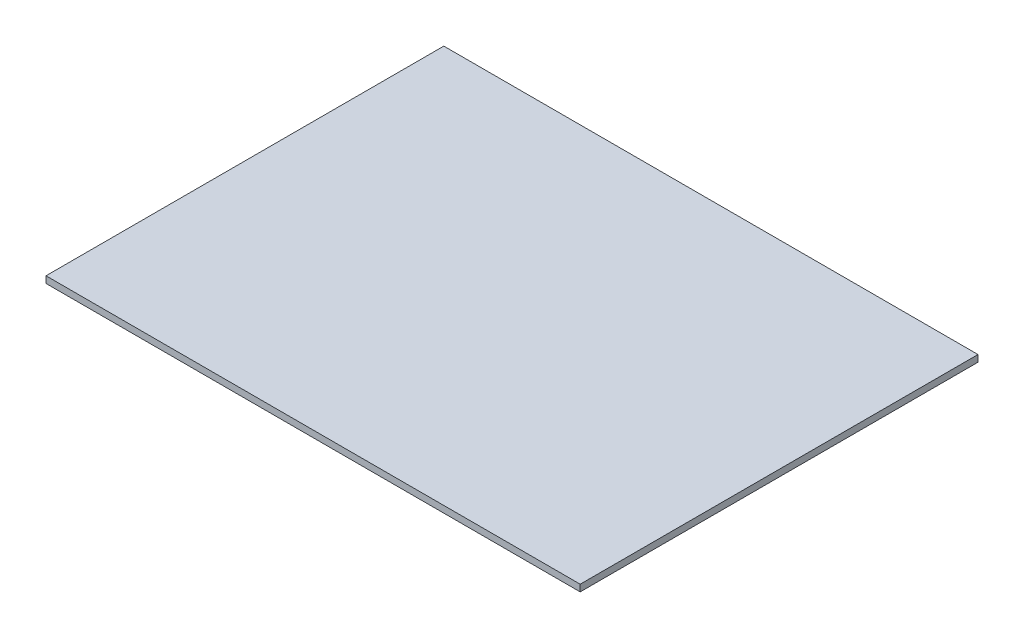
SolidWorks part; units mm, degrees
ref_plane "Front Plane" through (0, 0, 0) normal (0, 0, 1) x (1, 0, 0)
ref_plane "Top Plane" through (0, 0, 0) normal (0, 1, 0) x (1, 0, 0)
ref_plane "Right Plane" through (0, 0, 0) normal (1, 0, 0) x (0, 0, -1)
sketch "Sketch1" plane through (0, 0, 0) normal (0, 1, 0) x (1, 0, 0)
  line L1 (0, 0) -> (399.5, 0)
  line L2 (0, 0) -> (0, 297.5)
  line L3 (0, 297.5) -> (399.5, 297.5)
  line L4 (399.5, 0) -> (399.5, 297.5)
  dimension "D1" = 297.5
  dimension "D2" = 399.5
extrude "Boss-Extrude1" add sketch "Sketch1" along normal blind 5
